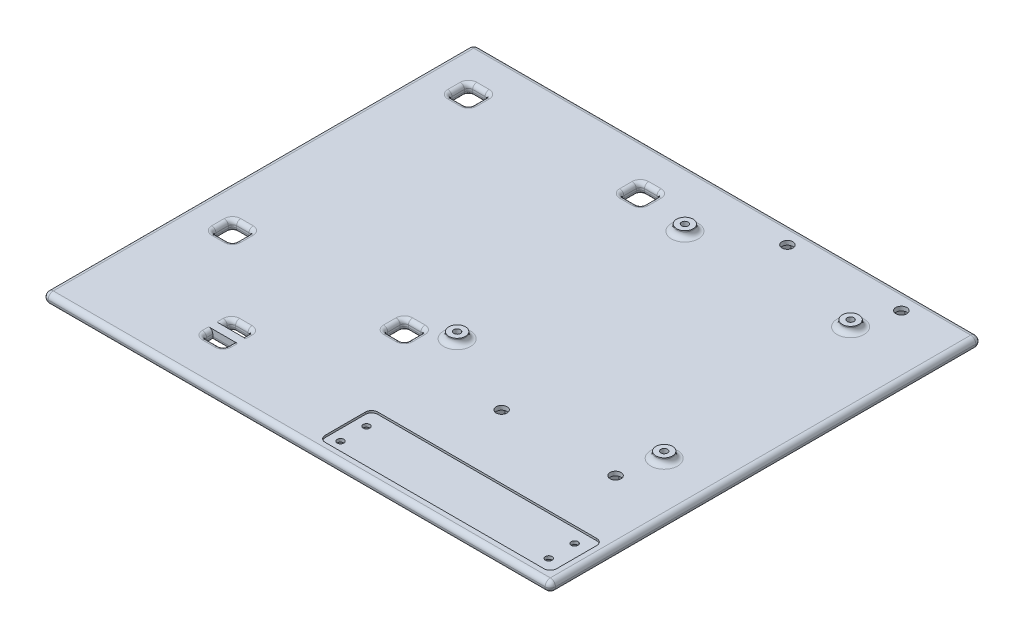
SolidWorks part; units mm, degrees
ref_plane "Plan de face" through (0, 0, 0) normal (0, 0, 1) x (1, 0, 0)
ref_plane "Plan de dessus" through (0, 0, 0) normal (0, 1, 0) x (1, 0, 0)
ref_plane "Plan de droite" through (0, 0, 0) normal (1, 0, 0) x (0, 0, -1)
sketch "Esquisse1" plane through (0, 0, 0) normal (0, 1, 0) x (1, 0, 0)
  line L5 (-60, 60) -> (60, 60)
  line L6 (-60, 60) -> (-60, -60)
  line L7 (-60, -60) -> (60, -60)
  line L8 (60, 60) -> (60, -60)
  line L9 (-60, 60) -> (60, -60) construction
  line L10 (-60, -60) -> (60, 60) construction
  point P0 (0, 0)
  dimension "D1" = 120
  dimension "D2" = 120
extrude "Boss.-Extru.1" add sketch "Esquisse1" along normal blind 5
sketch "Esquisse2" plane through (0, 5, 0) normal (0, 1, 0) x (1, 0, 0)
  line L1 (-55, 55) -> (55, 55) construction
  line L2 (-55, 55) -> (-55, -55) construction
  line L3 (-55, -55) -> (55, -55) construction
  line L4 (55, 55) -> (55, -55) construction
  line L5 (-55, 55) -> (55, -55) construction
  line L6 (-55, -55) -> (55, 55) construction
  circle A0 centre (-40, 50) radius 4
  circle A1 centre (40, 50) radius 4
  circle A2 centre (50, -50) radius 4
  circle A3 centre (-50, -50) radius 4
  point P0 (0, 0)
  dimension "D3" = 8
  dimension "D4" = 8
  dimension "D5" = 8
  dimension "D6" = 8
  dimension "D1" = 110
  dimension "D2" = 110
  dimension "D7" = 50
  dimension "D8" = 40
  dimension "D9" = 80
  dimension "D10" = 100
  dimension "D11" = 100
  dimension "D12" = 50
  dimension "D13" = 50
  dimension "D14" = 50
extrude "Boss.-Extru.2" add sketch "Esquisse2" along normal blind 3
sketch "Esquisse7" plane through (0, 0, 0) normal (0, 1, 0) x (1, 0, 0)
  line L0 (60, -60) -> (60, 60) construction
  line L2 (-170, 78) -> (-170, -130)
  line L3 (-170, -130) -> (75, -130)
  line L5 (-55, -55) -> (55, -55) construction
  line L6 (-60, 60) -> (-60, -60) construction
  line L13 (75, 78) -> (75, -130)
  line L14 (-170, 78) -> (75, 78)
  point P3 (0, 0)
  point P5 (0, 0)
  point P8 (75, 120)
  point P12 (0, 0)
  dimension "D1" = 15
  dimension "D2" = 75
  dimension "D3" = 208
  dimension "D4" = 110
extrude "Boss.-Extru.3" add sketch "Esquisse7" along normal blind 5
sketch "Esquisse8" plane through (0, 5, 0) normal (0, 1, 0) x (1, 0, 0)
  line L0 (-170, 0) -> (-55, 0) construction
  line L1 (-164.5, 70) -> (-60.5, 70) construction
  line L2 (-164.5, 70) -> (-164.5, -94) construction
  line L3 (-164.5, -94) -> (-60.5, -94) construction
  line L4 (-60.5, 70) -> (-60.5, -94) construction
  line L6 (-55, 55) -> (-55, -55) construction
  line L7 (-170, 78) -> (-170, -130) construction
  point P7 (-180, 0)
  point P11 (-112.5, 0)
  point P12 (-180, -20)
  dimension "D1" = 104
  dimension "D2" = 164
  dimension "D3" = 70
  dimension "D4" = 52
hole_wizard "Dégagement M31" positions "Esquisse3" profile "Esquisse4" hole size "M3" standard "Ansi Metric" end condition through all
sketch "Esquisse3" plane through (0, 8, 0) normal (0, 1, 0) x (1, 0, 0)
  point P0 (-40, 50)
  point P3 (40, 50)
  point P6 (50, -50)
  point P9 (-50, -50)
sketch "Esquisse4" plane through (-40, 8, -50) normal (1, 0, 0) x (0, 0, 1)
  line L0 (0, 0) -> (0, 8)
  line L1 (0, 8) -> (1.6, 8)
  line L2 (1.6, 8) -> (1.6, 0)
  line L5 (1.6, 0) -> (0, 0)
  line L11 (0, -6.35) -> (0, 107.95) construction
  dimension "Diamètre du perçage jusqu'au prochain" = 3.2
  dimension "Profondeur du perçage jusqu'au prochain" = 8
sketch "Esquisse5" plane through (0, 0, 0) normal (0, -1, 0) x (1, 0, 0)
  line L1 (-46.7668, 50) -> (-48.3834, 52.8)
  line L2 (-48.3834, 52.8) -> (-51.6166, 52.8)
  line L3 (-51.6166, 52.8) -> (-53.2332, 50)
  line L4 (-53.2332, 50) -> (-51.6166, 47.2)
  line L5 (-51.6166, 47.2) -> (-48.3834, 47.2)
  line L6 (-48.3834, 47.2) -> (-46.7668, 50)
  line L7 (53.2332, 50) -> (51.6166, 52.8)
  line L8 (51.6166, 52.8) -> (48.3834, 52.8)
  line L9 (48.3834, 52.8) -> (46.7668, 50)
  line L10 (46.7668, 50) -> (48.3834, 47.2)
  line L11 (48.3834, 47.2) -> (51.6166, 47.2)
  line L12 (51.6166, 47.2) -> (53.2332, 50)
  line L13 (-36.7668, -50) -> (-38.3834, -47.2)
  line L14 (-38.3834, -47.2) -> (-41.6166, -47.2)
  line L15 (-41.6166, -47.2) -> (-43.2332, -50)
  line L16 (-43.2332, -50) -> (-41.6166, -52.8)
  line L17 (-41.6166, -52.8) -> (-38.3834, -52.8)
  line L18 (-38.3834, -52.8) -> (-36.7668, -50)
  line L19 (43.2332, -50) -> (41.6166, -47.2)
  line L20 (41.6166, -47.2) -> (38.3834, -47.2)
  line L21 (38.3834, -47.2) -> (36.7668, -50)
  line L22 (36.7668, -50) -> (38.3834, -52.8)
  line L23 (38.3834, -52.8) -> (41.6166, -52.8)
  line L24 (41.6166, -52.8) -> (43.2332, -50)
  circle A0 centre (-50, 50) radius 2.8 construction
  circle A1 centre (50, 50) radius 2.8 construction
  circle A2 centre (-40, -50) radius 2.8 construction
  circle A3 centre (40, -50) radius 2.8 construction
  point P28 (-40, -52.8)
  dimension "D1" = 5.6
  dimension "D2" = 5.6
  dimension "D3" = 5.6
  dimension "D4" = 5.6
extrude "Enlèv. mat.-Extru.1" cut sketch "Esquisse5" against normal blind 3
sketch "Esquisse9" plane through (0, 5, 0) normal (0, 1, 0) x (1, 0, 0)
  line L0 (-170, -130) -> (75, -130) construction
  line L1 (70, -125) -> (-41.2961, -125) construction
  line L2 (70, -125) -> (70, -100) construction
  line L3 (70, -100) -> (-41.2961, -100) construction
  line L4 (-41.2961, -125) -> (-41.2961, -100) construction
  line L5 (60, -120) -> (60, 120) construction
  line L6 (70.2, -125.2) -> (-41.4961, -125.2)
  line L7 (-41.4961, -125.2) -> (-41.4961, -99.8)
  line L8 (70.2, -99.8) -> (-41.4961, -99.8)
  line L9 (70.2, -125.2) -> (70.2, -99.8)
  line L11 (50, -100) -> (67, -100) construction
  line L13 (70, -103) -> (70, -122) construction
  line L14 (15.9081, -125) -> (5.9081, -125) construction
  line L15 (-41.2961, -122) -> (-41.2961, -115) construction
  point P6 (0, 0)
  point P15 (54.9701, -85)
  point P16 (0, 0)
  point P17 (0, 0)
  dimension "D1" = 30
  dimension "D2" = 101.2961
  dimension "D5" = 0.2
extrude "Enlèv. mat.-Extru.2" cut sketch "Esquisse9" against normal blind 1
sketch "Esquisse10" plane through (0, 5, 0) normal (0, 1, 0) x (1, 0, 0)
  point P0 (63, -118.75)
  point P1 (63.0098, -106.2531)
  point P2 (0, 0)
  point P3 (0, 0)
  point P4 (-36.2661, -107.5)
  point P5 (0, 0)
  point P6 (0, 0)
  point P7 (-36.2961, -120)
  point P9 (0, 0)
  point P11 (-51.2961, -85)
  point P12 (-49.2961, -86.25)
  point P14 (-49.3059, -98.7469)
hole_wizard "Dégagement M32" positions "Esquisse11" profile "Esquisse12" hole size "M3" standard "Ansi Metric" end condition through all
sketch "Esquisse11" plane through (0, 4, 0) normal (0, 1, 0) x (1, 0, 0)
  point P0 (63, -118.75)
  point P3 (63.0098, -106.2531)
  point P6 (-36.2661, -107.5)
  point P9 (-36.2961, -120)
sketch "Esquisse12" plane through (63, 4, 118.75) normal (1, 0, 0) x (0, 0, 1)
  line L0 (0, 0) -> (0, 4)
  line L1 (0, 4) -> (1.6, 4)
  line L2 (1.6, 4) -> (1.6, 0)
  line L5 (1.6, 0) -> (0, 0)
  line L11 (0, -6.35) -> (0, 107.95) construction
  dimension "Diamètre du perçage jusqu'au prochain" = 3.2
  dimension "Profondeur du perçage jusqu'au prochain" = 4
sketch "Esquisse13" plane through (0, 0, 0) normal (0, -1, 0) x (-1, 0, 0)
  line L1 (-59.7766, -106.2531) -> (-61.3932, -103.4531)
  line L2 (-61.3932, -103.4531) -> (-64.6264, -103.4531)
  line L3 (-64.6264, -103.4531) -> (-66.243, -106.2531)
  line L4 (-66.243, -106.2531) -> (-64.6264, -109.0531)
  line L5 (-64.6264, -109.0531) -> (-61.3932, -109.0531)
  line L6 (-61.3932, -109.0531) -> (-59.7766, -106.2531)
  line L7 (-59.7668, -118.75) -> (-61.3834, -115.95)
  line L8 (-61.3834, -115.95) -> (-64.6166, -115.95)
  line L9 (-64.6166, -115.95) -> (-66.2332, -118.75)
  line L10 (-66.2332, -118.75) -> (-64.6166, -121.55)
  line L11 (-64.6166, -121.55) -> (-61.3834, -121.55)
  line L12 (-61.3834, -121.55) -> (-59.7668, -118.75)
  line L13 (37.9127, -122.8) -> (39.5292, -120)
  line L14 (39.5292, -120) -> (37.9127, -117.2)
  line L15 (37.9127, -117.2) -> (34.6795, -117.2)
  line L16 (34.6795, -117.2) -> (33.0629, -120)
  line L17 (33.0629, -120) -> (34.6795, -122.8)
  line L18 (34.6795, -122.8) -> (37.9127, -122.8)
  line L19 (37.8827, -110.3) -> (39.4993, -107.5)
  line L20 (39.4993, -107.5) -> (37.8827, -104.7)
  line L21 (37.8827, -104.7) -> (34.6496, -104.7)
  line L22 (34.6496, -104.7) -> (33.033, -107.5)
  line L23 (33.033, -107.5) -> (34.6496, -110.3)
  line L24 (34.6496, -110.3) -> (37.8827, -110.3)
  circle A0 centre (-63.0098, -106.2531) radius 2.8 construction
  circle A1 centre (-63, -118.75) radius 2.8 construction
  circle A2 centre (36.2961, -120) radius 2.8 construction
  circle A3 centre (36.2661, -107.5) radius 2.8 construction
  dimension "D1" = 5.6
  dimension "D2" = 5.6
  dimension "D3" = 5.6
  dimension "D4" = 5.6
extrude "Enlèv. mat.-Extru.3" cut sketch "Esquisse13" against normal blind 2.5
sketch "Esquisse14" plane through (0, 5, 0) normal (0, 1, 0) x (1, 0, 0)
  line L0 (-25, -63) -> (-25, -25) construction
  line L1 (-55, -55) -> (55, 55) construction
  line L2 (-25, -25) -> (-63, -25) construction
  line L3 (-63, -25) -> (-63, 40) construction
  line L4 (-63, 40) -> (-40, 40) construction
  line L5 (-40, 40) -> (-40, 63) construction
  line L6 (-40, 63) -> (60, 63) construction
  line L8 (60, 63) -> (60, -63) construction
  line L9 (60, -63) -> (-25, -63) construction
  line L12 (-55, 55) -> (55, 55) construction
  line L13 (-55, 55) -> (-55, -55) construction
  line L14 (-55, -55) -> (55, -55) construction
  point P18 (0, 0)
  point P19 (0, 0)
  dimension "D1" = 15
  dimension "D2" = 15
  dimension "D3" = 30
  dimension "D4" = 30
  dimension "D5" = 8
  dimension "D6" = 8
  dimension "D7" = 8
hole_wizard "Dégagement M51" positions "Esquisse15" profile "Esquisse16" hole size "M5" standard "Ansi Metric" end condition through all
sketch "Esquisse15" plane through (0, 5, 0) normal (0, 1, 0) x (1, 0, 0)
  point P0 (-9.5, 69)
  point P3 (45.5, 69)
  point P6 (-9.5, -69)
  point P9 (45.5, -69)
sketch "Esquisse16" plane through (-9.5, 5, -69) normal (1, 0, 0) x (0, 0, 1)
  line L0 (0, 0) -> (0, 5)
  line L1 (0, 5) -> (2.65, 5)
  line L2 (2.65, 5) -> (2.65, 0)
  line L5 (2.65, 0) -> (0, 0)
  line L11 (0, -6.35) -> (0, 107.95) construction
  dimension "Diamètre du perçage jusqu'au prochain" = 5.3
  dimension "Profondeur du perçage jusqu'au prochain" = 5
ref_plane "Plan1" through (-108, 0, 0) normal (-1, 0, 0) x (0, 0, 1)
sketch "Esquisse17" plane through (0, 5, 0) normal (0, 1, 0) x (1, 0, 0)
  line L0 (-164.5, 70) -> (-164.5, -94) construction
  line L1 (-154.5, 50) -> (-144.5, 50)
  line L2 (-154.5, 50) -> (-154.5, 60)
  line L3 (-154.5, 60) -> (-144.5, 60)
  line L4 (-144.5, 50) -> (-144.5, 60)
  line L5 (-154.5, 50) -> (-144.5, 60) construction
  line L6 (-154.5, 60) -> (-144.5, 50) construction
  line L7 (-164.5, 70) -> (-60.5, 70) construction
  line L8 (-164.5, -94) -> (-60.5, -94) construction
  line L9 (-154.5, -54) -> (-144.5, -54)
  line L10 (-154.5, -54) -> (-154.5, -64)
  line L11 (-154.5, -64) -> (-144.5, -64)
  line L12 (-144.5, -54) -> (-144.5, -64)
  line L13 (-154.5, -54) -> (-144.5, -64) construction
  line L14 (-154.5, -64) -> (-144.5, -54) construction
  line L15 (-108, 2.75) -> (-108, -2.75) construction
  line L16 (-61.5, -64) -> (-71.5, -54) construction
  line L17 (-61.5, -54) -> (-71.5, -64) construction
  line L18 (-61.5, 60) -> (-71.5, 50) construction
  line L19 (-61.5, 50) -> (-71.5, 60) construction
  line L20 (-71.5, -54) -> (-71.5, -64)
  line L21 (-61.5, -64) -> (-71.5, -64)
  line L22 (-61.5, -54) -> (-61.5, -64)
  line L23 (-61.5, -54) -> (-71.5, -54)
  line L24 (-71.5, 50) -> (-71.5, 60)
  line L25 (-61.5, 60) -> (-71.5, 60)
  line L26 (-61.5, 50) -> (-61.5, 60)
  line L27 (-61.5, 50) -> (-71.5, 50)
  point P0 (-149.5, 55)
  point P9 (-149.5, -59)
  point P14 (-143.7802, -67.046)
  point P27 (-66.5, -59)
  point P28 (-66.5, 55)
  dimension "D1" = 10
  dimension "D2" = 10
  dimension "D3" = 10
  dimension "D4" = 10
  dimension "D5" = 10
  dimension "D6" = 10
  dimension "D7" = 10
  dimension "D8" = 30
extrude "Enlèv. mat.-Extru.4" cut sketch "Esquisse17" against normal up to surface (5 mm away) up to face at (-9.5, 0, -66.35)
sketch "Esquisse18" plane through (0, 0, 0) normal (0, -1, 0) x (-1, 0, 0)
  line L1 (11.8601, 73.0373) -> (7.1836, 73.0626)
  line L2 (7.1836, 73.0626) -> (4.8235, 69.0252)
  line L3 (4.8235, 69.0252) -> (7.1399, 64.9627)
  line L4 (7.1399, 64.9627) -> (11.8164, 64.9374)
  line L5 (11.8164, 64.9374) -> (14.1765, 68.9748)
  line L6 (14.1765, 68.9748) -> (11.8601, 73.0373)
  line L7 (-43.1399, 73.0373) -> (-47.8164, 73.0626)
  line L8 (-47.8164, 73.0626) -> (-50.1765, 69.0252)
  line L9 (-50.1765, 69.0252) -> (-47.8601, 64.9627)
  line L10 (-47.8601, 64.9627) -> (-43.1836, 64.9374)
  line L11 (-43.1836, 64.9374) -> (-40.8235, 68.9748)
  line L12 (-40.8235, 68.9748) -> (-43.1399, 73.0373)
  line L13 (-40.8235, -69) -> (-43.1617, -64.95)
  line L14 (-43.1617, -64.95) -> (-47.8383, -64.95)
  line L15 (-47.8383, -64.95) -> (-50.1765, -69)
  line L16 (-50.1765, -69) -> (-47.8383, -73.05)
  line L17 (-47.8383, -73.05) -> (-43.1617, -73.05)
  line L18 (-43.1617, -73.05) -> (-40.8235, -69)
  line L19 (14.1765, -69) -> (11.8383, -64.95)
  line L20 (11.8383, -64.95) -> (7.1617, -64.95)
  line L21 (7.1617, -64.95) -> (4.8235, -69)
  line L22 (4.8235, -69) -> (7.1617, -73.05)
  line L23 (7.1617, -73.05) -> (11.8383, -73.05)
  line L24 (11.8383, -73.05) -> (14.1765, -69)
  circle A0 centre (9.5, 69) radius 4.05 construction
  circle A1 centre (-45.5, 69) radius 4.05 construction
  circle A2 centre (-45.5, -69) radius 4.05 construction
  circle A3 centre (9.5, -69) radius 4.05 construction
  dimension "D1" = 8.1
  dimension "D2" = 8.1
  dimension "D3" = 8.1
  dimension "D4" = 8.1
extrude "Enlèv. mat.-Extru.5" cut sketch "Esquisse18" against normal blind 3
sketch "Esquisse20" plane through (0, 5, 0) normal (0, 1, 0) x (1, 0, 0)
  line L1 (-113, -105) -> (-103, -105)
  line L2 (-113, -105) -> (-113, -110)
  line L3 (-113, -110) -> (-103, -110)
  line L4 (-103, -105) -> (-103, -110)
  line L5 (-113, -105) -> (-103, -110) construction
  line L6 (-113, -110) -> (-103, -105) construction
  line L7 (-108, 2.75) -> (-108, -2.75) construction
  line L12 (-170, -130) -> (75, -130) construction
  line L13 (-113, -96) -> (-103, -96)
  line L14 (-113, -96) -> (-113, -101)
  line L15 (-113, -101) -> (-103, -101)
  line L16 (-103, -96) -> (-103, -101)
  line L17 (-113, -96) -> (-103, -101) construction
  line L18 (-113, -101) -> (-103, -96) construction
  point P0 (-108, -107.5)
  point P5 (-118, -100.2891)
  point P8 (-108, -98.5)
  dimension "D1" = 10
  dimension "D2" = 5
  dimension "D3" = 5
  dimension "D4" = 10
  dimension "D5" = 4
  dimension "D6" = 20
extrude "Enlèv. mat.-Extru.6" cut sketch "Esquisse20" against normal up to surface (5 mm away) up to face at (-9.5, 0, 69)
fillet "Congé1" radius 2 66 edges at (-144.5, 0, -55) (-144.5, 5, -55) (-154.5, 5, -55) (-154.5, 0, -55) (-71.5, 0, -55) (-71.5, 5, -55) (-61.5, 5, -55) (-61.5, 0, -55) (-61.5, 0, 59) (-61.5, 5, 59) (-71.5, 5, 59) (-71.5, 0, 59) (-154.5, 0, 59) (-154.5, 5, 59) (-144.5, 5, 59) (-144.5, 0, 59) (-154.5, 2.5, -60) (-149.5, 5, -60) (-144.5, 2.5, -60) (-149.5, 0, -60) (-144.5, 2.5, -50) (-149.5, 5, -50) (-154.5, 2.5, -50) (-149.5, 0, -50) (-61.5, 2.5, -50) (-66.5, 5, -50) (-71.5, 2.5, -50) (-66.5, 0, -50) (-71.5, 2.5, -60) (-66.5, 5, -60) (-61.5, 2.5, -60) (-66.5, 0, -60) (-71.5, 2.5, 54) (-66.5, 5, 54) (-61.5, 2.5, 54) (-66.5, 0, 54) (-61.5, 2.5, 64) (-66.5, 5, 64) (-71.5, 2.5, 64) (-66.5, 0, 64) (-144.5, 2.5, 64) (-149.5, 5, 64) (-154.5, 2.5, 64) (-149.5, 0, 64) (-154.5, 2.5, 54) (-149.5, 5, 54) (-144.5, 2.5, 54) (-149.5, 0, 54) (-113, 0, 107.5) (-113, 5, 107.5) (-103, 5, 107.5) (-103, 0, 107.5) (-113, 0, 98.5) (-113, 5, 98.5) (-103, 5, 98.5) (-103, 0, 98.5) (-103, 2.5, 110) (-108, 5, 110) (-113, 2.5, 110) (-108, 0, 110) (-108, 0, 101) (-108, 0, 105) (-113, 2.5, 96) (-108, 5, 96) (-103, 2.5, 96) (-108, 0, 96)
fillet "Congé2" radius 2.5 8 edges at (75, 0, 26) (75, 5, 26) (-47.5, 0, -78) (-47.5, 5, -78) (-47.5, 0, 130) (-47.5, 5, 130) (-170, 0, 26) (-170, 5, 26)
fillet "Congé3" radius 2.5 4 edges at (40, 5, -46) (-40, 5, -46) (50, 5, 54) (-50, 5, 54)
fillet "Congé4" radius 3 4 edges at (70.2, 4.5, 125.2) (-41.4961, 4.5, 125.2) (70.2, 4.5, 99.8) (-41.4961, 4.5, 99.8)
